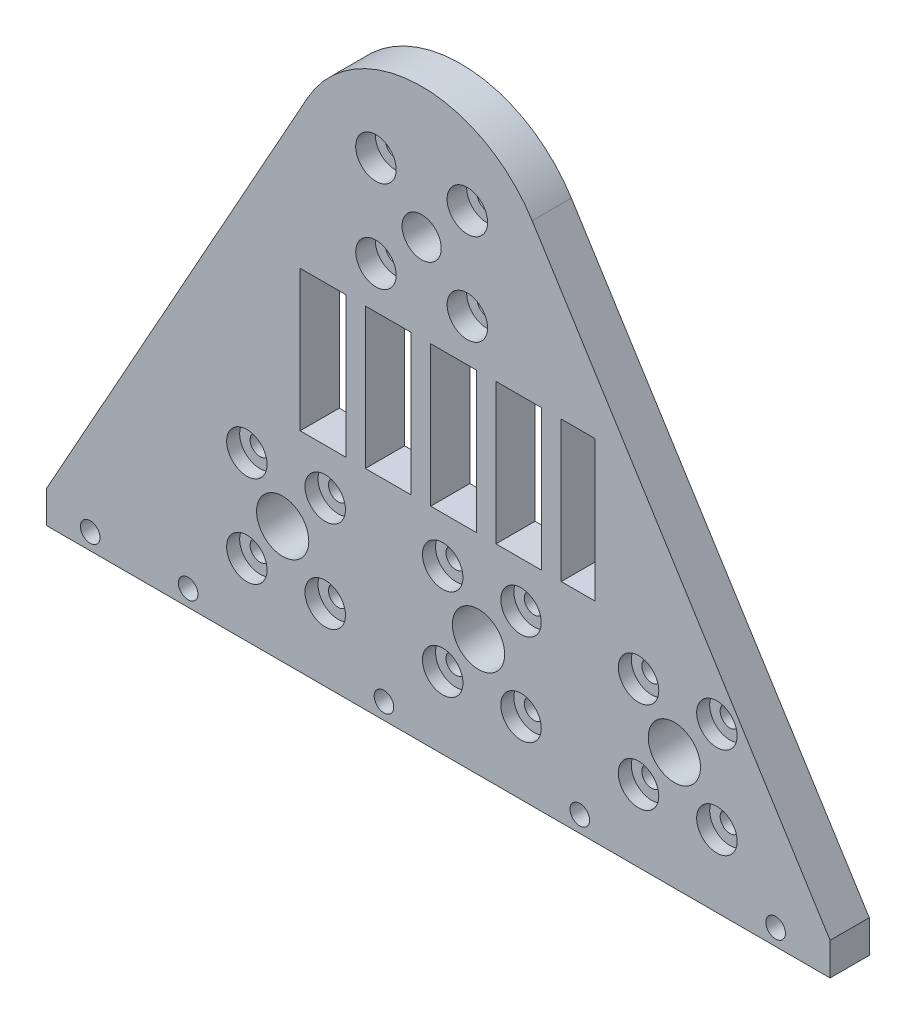
SolidWorks part; units mm, degrees
ref_plane "前视基准面" through (0, 0, 0) normal (0, 0, 1) x (1, 0, 0)
ref_plane "上视基准面" through (0, 0, 0) normal (0, 1, 0) x (1, 0, 0)
ref_plane "右视基准面" through (0, 0, 0) normal (1, 0, 0) x (0, 0, -1)
other "Configuration Table"
sketch "草图1" plane through (0, 0, 0) normal (0, 0, 1) x (1, 0, 0)
  line L5 (53.2118, 15.1053) -> (98.8463, -57.534)
  line L6 (18.8044, 14.1987) -> (-21.1537, -57.534)
  line L9 (98.8463, -57.534) -> (98.8463, -62.534)
  line L10 (98.8463, -62.534) -> (-21.1537, -62.534)
  line L11 (-21.1537, -62.534) -> (-21.1537, -57.534)
  arc A0 (53.2118, 15.1053) -> (18.8044, 14.1987) centre (36.2765, 4.466) ccw
  circle A2 centre (36.2765, 4.466) radius 3
  point P0 (0, 0)
extrude "凸台-拉伸1" add sketch "草图1" along normal blind 6
sketch "草图2" plane through (0, 0, 6) normal (0, 0, 1) x (1, 0, 0)
  line L0 (36.2765, 4.466) -> (36.2765, 16.549) construction
  line L5 (36.2765, 4.466) -> (44.4343, 4.466) construction
  circle A2 centre (29.2765, 11.466) radius 3.1
  circle A3 centre (43.2765, 11.466) radius 3.1
  circle A4 centre (43.2765, -2.534) radius 3.1
  circle A5 centre (29.2765, -2.534) radius 3.1
extrude "切除-拉伸6" cut sketch "草图2" against normal blind 3
sketch "草图4" plane through (0, 0, 3) normal (0, 0, 1) x (1, 0, 0)
  circle A0 centre (43.2765, 11.466) radius 1.5 construction
  circle A1 centre (43.2765, 11.466) radius 1.5
  circle A2 centre (43.2765, -2.534) radius 1.5 construction
  circle A3 centre (43.2765, -2.534) radius 1.5
  circle A4 centre (29.2765, -2.534) radius 1.5 construction
  circle A5 centre (29.2765, -2.534) radius 1.5
  circle A6 centre (29.2765, 11.466) radius 1.5 construction
  circle A7 centre (29.2765, 11.466) radius 1.5
extrude "切除-拉伸7" cut sketch "草图4" against normal through all
sketch "草图5" plane through (0, 0, 6) normal (0, 0, 1) x (1, 0, 0)
  line L0 (24.6608, -8.9774) -> (24.6608, -30.534)
  line L1 (14.6608, -8.9774) -> (62.8566, -8.9774)
  line L2 (14.6608, -8.9774) -> (14.6608, -30.534)
  line L3 (14.6608, -30.534) -> (62.8566, -30.534)
  line L4 (62.8566, -8.9774) -> (62.8566, -30.534)
  line L5 (14.6608, -8.9774) -> (17.6608, -8.9774)
  line L6 (14.6608, -8.9774) -> (14.6608, -30.534)
  line L7 (14.6608, -30.534) -> (17.6608, -30.534)
  line L8 (17.6608, -8.9774) -> (17.6608, -30.534)
  line L9 (24.6608, -8.9774) -> (27.6608, -8.9774)
  line L10 (27.6608, -8.9774) -> (27.6608, -30.534)
  line L11 (24.6608, -30.534) -> (27.6608, -30.534)
  line L12 (34.6608, -8.9774) -> (34.6608, -30.534)
  line L13 (34.6608, -8.9774) -> (37.6608, -8.9774)
  line L14 (37.6608, -8.9774) -> (37.6608, -30.534)
  line L15 (34.6608, -30.534) -> (37.6608, -30.534)
  line L16 (44.6608, -8.9774) -> (44.6608, -30.534)
  line L17 (44.6608, -8.9774) -> (47.6608, -8.9774)
  line L18 (47.6608, -8.9774) -> (47.6608, -30.534)
  line L19 (44.6608, -30.534) -> (47.6608, -30.534)
  line L20 (54.6608, -8.9774) -> (54.6608, -30.534)
  line L21 (54.6608, -8.9774) -> (57.6608, -8.9774)
  line L22 (57.6608, -8.9774) -> (57.6608, -30.534)
  line L23 (54.6608, -30.534) -> (57.6608, -30.534)
  circle A0 centre (36.2765, 4.466) radius 20 construction
  circle A1 centre (14.9882, -44.534) radius 4 construction
  circle A2 centre (14.9882, -44.534) radius 4
  circle A3 centre (44.9882, -44.534) radius 4 construction
  circle A4 centre (44.9882, -44.534) radius 4
  circle A5 centre (74.9882, -44.534) radius 4 construction
  circle A6 centre (74.9882, -44.534) radius 4
  dimension "D1" = 3
  dimension "D3" = 5.1958
  dimension "D4" = 35
  dimension "D2" = 5
extrude "切除-拉伸8" cut sketch "草图5" against normal up to next contours L1 L8 L3 L0 | L12 L1 L10 L3 | L16 L1 L14 L3 | L20 L1 L18 L3 | L1 L22 L3 L4 | A2 | A4 | A6 region at (21.1608, -19.7557, 6) region at (31.1608, -19.7557, 6) region at (41.1608, -19.7557, 6) region at (51.1608, -19.7557, 6) region at (60.2587, -19.7557, 6) region at (14.9882, -44.534, 6) region at (44.9882, -44.534, 6) region at (74.9882, -44.534, 6)
sketch "草图6" plane through (0, 0, 6) normal (0, 0, 1) x (1, 0, 0)
  circle A0 centre (21.5023, -37.534) radius 3.1
  circle A1 centre (9.5023, -37.534) radius 3.1
  circle A2 centre (9.5023, -51.534) radius 3.1
  circle A3 centre (21.5023, -51.534) radius 3.1
  circle A4 centre (39.5023, -37.534) radius 3.1
  circle A5 centre (51.5023, -37.534) radius 3.1
  circle A6 centre (51.5023, -51.534) radius 3.1
  circle A7 centre (39.5023, -51.534) radius 3.1
  circle A8 centre (69.5023, -37.534) radius 3.1
  circle A9 centre (81.5023, -37.534) radius 3.1
  circle A10 centre (81.5023, -51.534) radius 3.1
  circle A11 centre (69.5023, -51.534) radius 3.1
  dimension "D1" = 3
extrude "切除-拉伸9" cut sketch "草图6" against normal blind 2
sketch "草图7" plane through (0, 0, 4) normal (0, 0, 1) x (1, 0, 0)
  circle A0 centre (9.5023, -37.534) radius 1.5
  circle A1 centre (21.5023, -37.534) radius 1.5
  circle A2 centre (9.5023, -51.534) radius 1.5
  circle A3 centre (21.5023, -51.534) radius 1.5
  circle A4 centre (51.5023, -51.534) radius 1.5
  circle A5 centre (39.5023, -51.534) radius 1.5
  circle A6 centre (39.5023, -37.534) radius 1.5
  circle A7 centre (51.5023, -37.534) radius 1.5
  circle A8 centre (81.5023, -51.534) radius 1.5
  circle A9 centre (69.5023, -51.534) radius 1.5
  circle A10 centre (69.5023, -37.534) radius 1.5
  circle A11 centre (81.5023, -37.534) radius 1.5
extrude "切除-拉伸10" cut sketch "草图7" against normal through all
sketch "草图8" plane through (0, 0, 6) normal (0, 0, 1) x (1, 0, 0)
  circle A0 centre (90.5023, -60.034) radius 1.5 construction
  circle A1 centre (90.5023, -60.034) radius 1.5
  circle A2 centre (60.5023, -60.034) radius 1.5 construction
  circle A3 centre (60.5023, -60.034) radius 1.5
  circle A4 centre (30.5023, -60.034) radius 1.5 construction
  circle A5 centre (30.5023, -60.034) radius 1.5
  circle A6 centre (0.5023, -60.034) radius 1.5 construction
  circle A7 centre (0.5023, -60.034) radius 1.5
  circle A8 centre (-14.4977, -60.034) radius 1.5 construction
  circle A9 centre (-14.4977, -60.034) radius 1.5
extrude "切除-拉伸11" cut sketch "草图8" against normal through all
